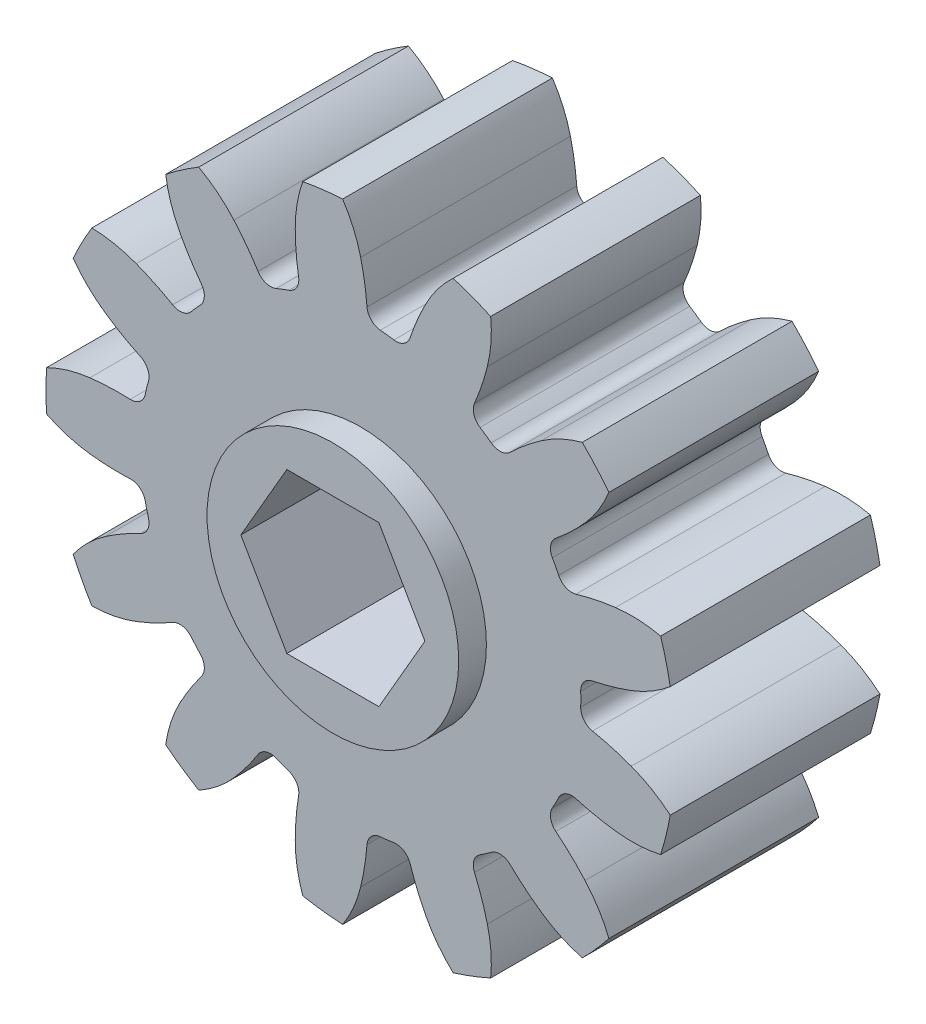
SolidWorks part; units mm, degrees
material "PLA/ABS"
ref_plane "Front" through (0, 0, 0) normal (0, 0, 1) x (1, 0, 0)
ref_plane "Top" through (0, 0, 0) normal (0, 1, 0) x (1, 0, 0)
ref_plane "Right" through (0, 0, 0) normal (1, 0, 0) x (0, 0, -1)
sketch "Sketch1" plane through (0, 0, 0) normal (0, 0, 1) x (1, 0, 0)
  line L0 (0, 0) -> (8.255, 0) construction
  line L1 (8.255, 0) -> (9.525, 0) construction
  circle A0 centre (0, 0) radius 8.255 construction
  circle A1 centre (0, 0) radius 9.525
  dimension "D1" = 16.51
  dimension "D2" = 1.27
extrude "Round Stock" add sketch "Sketch1" along normal mid plane 6.35
sketch "Sketch2" plane through (0, 0, 3.175) normal (0, 0, 1) x (1, 0, 0)
  line L0 (0, 0) -> (6.6675, 0) construction
  line L1 (6.6675, 0) -> (8.255, 0) construction
  line L2 (0, 0) -> (-9.525, 0) construction
  line L3 (0, 0) -> (-8.434, -4.4265) construction
  line L4 (-8.6992, -3.8793) -> (-7.7195, -2.9249) construction
  line L5 (-7.7195, -2.9249) -> (-6.3199, -2.1249) construction
  line L6 (-9.5056, -0.6078) -> (-8.1945, -0.9976) construction
  line L7 (-8.1945, -0.9976) -> (-6.5834, -1.0555) construction
  line L8 (-7.2559, -3.8082) -> (-7.7195, -2.9249) construction
  line L9 (-8.1945, -0.9976) -> (-8.1945, 0) construction
  line L12 (0, 0) -> (-8.1945, -0.9976) construction
  line L13 (0, 0) -> (-7.7195, -2.9249) construction
  line L14 (-7.7195, -2.9249) -> (-6.0358, -7.3685) construction
  line L15 (-8.1945, -0.9976) -> (-8.7688, 3.7195) construction
  line L16 (-7.7195, -2.9249) -> (-8.1945, -0.9976) construction
  line L17 (-6.4738, -1.5956) -> (-6.5834, -1.0555) construction
  line L18 (-6.4738, -1.5956) -> (-6.3199, -2.1249) construction
  circle A0 centre (0, 0) radius 8.255 construction
  circle A1 centre (0, 0) radius 6.6675 construction
  circle A2 centre (0, 0) radius 9.525 construction
  arc A3 (-8.6992, -3.8793) -> (-9.5056, -0.6078) centre (0, 0) cw
  arc A4 (-6.3199, -2.1249) -> (-6.5834, -1.0555) centre (0, 0) cw construction
  arc A6 (-8.6992, -3.8793) -> (-7.7195, -2.9249) centre (-5.4661, -6.218) cw
  arc A7 (-9.5056, -0.6078) -> (-8.1945, -0.9976) centre (-7.7296, 2.9656) ccw
  arc A8 (-7.7195, -2.9249) -> (-6.6596, -2.3175) centre (-3.3876, -9.2555) cw
  arc A9 (-8.1945, -0.9976) -> (-6.9738, -1.0428) centre (-7.3008, 6.621) ccw
  arc A10 (-6.6596, -2.3175) -> (-6.4211, -1.7957) centre (-6.8492, -1.9154) ccw
  arc A11 (-6.9738, -1.0428) -> (-6.5201, -1.394) centre (-6.9548, -1.4869) cw
  arc A12 (-6.4211, -1.7957) -> (-6.5201, -1.394) centre (0, 0) cw
  dimension "D6" = 16.51
  dimension "D9" = 0.4445
  dimension "D12" = 3.9903
  dimension "D2" = 1.5875
  dimension "D3" = 27.692
  dimension "D4" = 0.9976
  dimension "D5" = 0.9976
  dimension "D11" = 1.985
  dimension "D8" = 14.5
  dimension "D7" = 14.5
  dimension "D14" = 9
  dimension "D15" = 9
extrude "Single Tooth" cut sketch "Sketch2" against normal through all
ref_axis "Axis" through (0, 0, 50) along (0, 0, -1)
pattern_circular "Tooth Pattern" count 13 over 360 about axis through (0, 0, 50) along (0, 0, -1) of "Single Tooth"
sketch "Sketch4" plane through (0, 0, 3.175) normal (0, 0, 1) x (1, 0, 0)
  circle A0 centre (0, 0) radius 3.1039
  dimension "D1" = 6.2078
extrude "TopBearingBoss" [suppressed] add sketch "Sketch4" along normal blind 0.635
mirror "BottomBearingBoss" [suppressed] about plane through (0, 0, 0) normal (0, 0, 1)
sketch "Sketch6" [suppressed] plane through (0, 0, 0) normal (0, 0, 1) x (1, 0, 0)
  line L1 (1.4005, 2.4257) -> (-1.4005, 2.4257)
  line L2 (-1.4005, 2.4257) -> (-2.801, 0)
  line L3 (-2.801, 0) -> (-1.4005, -2.4257)
  line L4 (-1.4005, -2.4257) -> (1.4005, -2.4257)
  line L5 (1.4005, -2.4257) -> (2.801, 0)
  line L6 (2.801, 0) -> (1.4005, 2.4257)
  circle A0 centre (0, 0) radius 2.4257 construction
  circle A1 centre (0, 0) radius 2.4257 construction
extrude "Hex" [suppressed] cut sketch "Sketch6" against normal through all both and the other way through all
sketch "Sketch7" plane through (0, 0, -3.175) normal (0, 0, -1) x (-1, 0, 0)
  line L1 (1.3931, -2.413) -> (2.7863, 0)
  line L2 (2.7863, 0) -> (1.3931, 2.413)
  line L3 (1.3931, 2.413) -> (-1.3931, 2.413)
  line L4 (-1.3931, 2.413) -> (-2.7863, 0)
  line L5 (-2.7863, 0) -> (-1.3931, -2.413)
  line L6 (-1.3931, -2.413) -> (1.3931, -2.413)
  circle A0 centre (0, 0) radius 2.413 construction
  dimension "D1" = 4.826
extrude "Cut-Extrude1" cut sketch "Sketch7" against normal through all
sketch "Sketch8" plane through (0, 0, 3.175) normal (0, 0, 1) x (1, 0, 0)
  line L6 (-1.3931, -2.413) -> (1.3931, -2.413)
  line L7 (-2.7863, 0) -> (-1.3931, -2.413)
  line L8 (-1.3931, 2.413) -> (-2.7863, 0)
  line L9 (1.3931, 2.413) -> (-1.3931, 2.413)
  line L10 (2.7863, 0) -> (1.3931, 2.413)
  line L11 (1.3931, -2.413) -> (2.7863, 0)
  line L12 (-1.3931, -2.413) -> (1.3931, -2.413)
  line L13 (-2.7863, 0) -> (-1.3931, -2.413)
  line L14 (-1.3931, 2.413) -> (-2.7863, 0)
  line L15 (1.3931, 2.413) -> (-1.3931, 2.413)
  line L16 (2.7863, 0) -> (1.3931, 2.413)
  line L17 (1.3931, -2.413) -> (2.7863, 0)
  circle A0 centre (0, 0) radius 3.81
  dimension "D2" = 7.62
  dimension "D1" = 0
extrude "Boss-Extrude1" add sketch "Sketch8" along normal blind 0.8382
equation "\"N_teeth\"= \"No_Teeth\""
equation "\"pitch_diameter\"= \"N_teeth\" / \"Pitch\""
equation "\"Pd\"=\"N_teeth\"/\"pitch_diameter\""
equation "\"addendum\"=1.000/\"Pd\""
equation "\"face_width\"=0.25"
equation "\"deddendum\"=1.250/\"Pd\""
equation "\"D3@Sketch2\" = 360/\"N_teeth\""
equation "\"tooth_thickness\"=1.571/\"Pd\""
equation "\"D4@Sketch2\" = \"tooth_thickness\"/2"
equation "\"D5@Sketch2\" = \"tooth_thickness\"/2"
equation "\"Pressure_Angle\"= iif ( \"Pitch\" = 20 , 14.500000 , iif ( \"Pitch\" = 32 , 20 , 20 ) )"
equation "\"base_fillet\"=0.35/\"Pd\""
equation "\"D12@Sketch2\" = 2*\"tooth_thickness\""
equation "\"hub_projection\"=0.250000"
equation "\"sss_diam\"= 0.062500"
equation "\"D1@Sketch1\"=\"pitch_diameter\""
equation "\"D2@Sketch1\"=\"addendum\""
equation "\"D1@Round Stock\" = \"face_width\""
equation "\"D2@Sketch2\"=\"deddendum\""
equation "\"D6@Sketch2\"=\"pitch_diameter\""
equation "\"D7@Sketch2\"=\"Pressure_Angle\""
equation "\"D8@Sketch2\"=\"D7@Sketch2\""
equation "\"D9@Sketch2\"=\"base_fillet\""
equation "\"D1@Tooth Pattern\" = \"N_teeth\""
equation "\"Pitch\"= \"GearPitch\""
equation "\"BossDia\"= \"BoreDia\" * 1.3"
equation "\"Hex\"= iif ( \"HexBore\" = 1 , \"unsuppressed\" , \"suppressed\" )"
equation "\"TopBearingBoss\" = iif ( \"Bearing_Boss\" = 0 , \"suppressed\" , \"unsuppressed\" )"
equation "\"BottomBearingBoss\"= iif ( \"Bearing_Boss\" > 1 , \"unsuppressed\" , \"suppressed\" )"
equation "\"D1@Sketch4\"=\"BossDia\""
equation "\"ToothCount\"= iif ( \"No_Teeth\" < 22 , \"suppressed\" , \"unsuppressed\" )"
